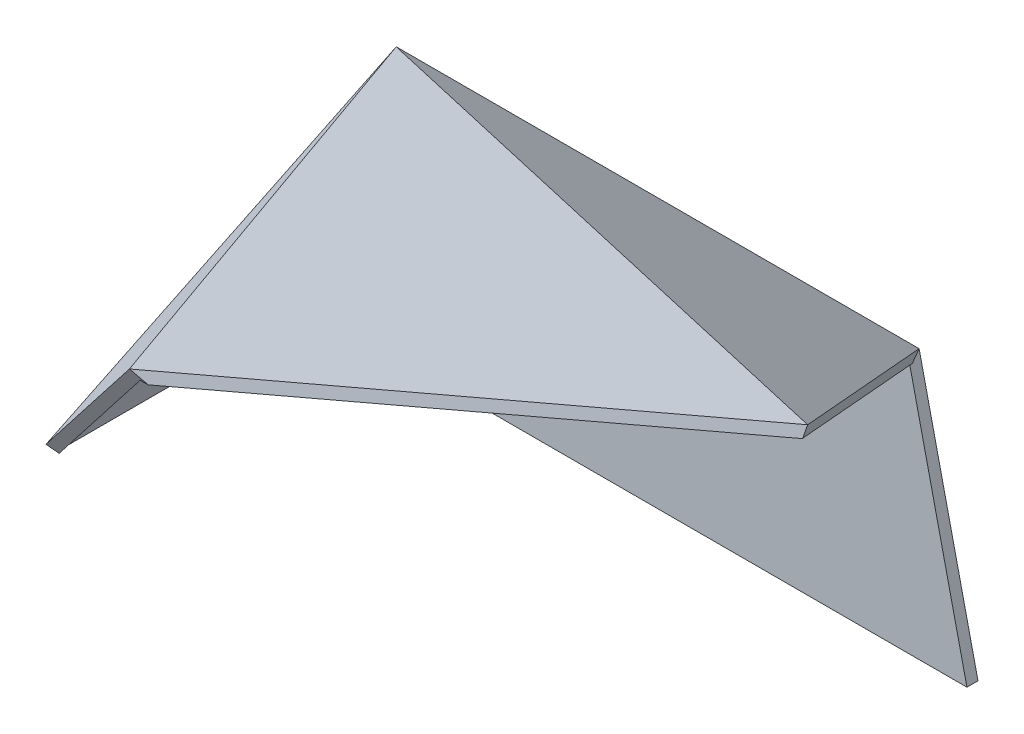
SolidWorks part; units mm, degrees
ref_plane "前视基准面" through (0, 0, 0) normal (0, 0, 1) x (1, 0, 0)
ref_plane "上视基准面" through (0, 0, 0) normal (0, 1, 0) x (1, 0, 0)
ref_plane "右视基准面" through (0, 0, 0) normal (1, 0, 0) x (0, 0, -1)
sketch "Sketch1" plane through (0, 0, 0) normal (0, 0, 1) x (1, 0, 0)
  line L0 (-295, -10) -> (-113.1586, -10)
  line L1 (-295, -10) -> (295, -10) construction
  line L2 (-113.1586, -10) -> (-129.1191, 60)
  line L3 (-129.1191, 60) -> (-270.8573, 60)
  line L4 (-270.8573, 60) -> (-295, -10)
  line L5 (-55, -10) -> (-295, -10) construction
  point P6 (-119.1255, 69.147)
  point P8 (-138.6835, -10)
  point P9 (-123.2439, 67.2585)
  point P10 (-98.3304, -10)
  point P13 (-129.1191, 68.9505)
  point P14 (-113.1586, -10)
  point P15 (-234.923, 70)
  point P16 (-260.891, 50)
  point P17 (-277.8307, 50)
  point P18 (-270.8573, 60)
  dimension "D1" = 70
extrude "Extrude1" add sketch "Sketch1" against normal blind 3
sketch "Sketch2" plane through (-260.5569, 89.8651, 0) normal (-0.9454, 0.326, 0) x (0, 0, 1)
  line L0 (0, -31.5915) -> (0, -105.6379)
  line L1 (0, -31.5915) -> (0, -105.6379) construction
  line L2 (0, -105.6379) -> (67.7928, -105.6379)
  line L5 (0, -31.5915) -> (67.7928, -105.6379)
  point P6 (0, -154.4847)
extrude "Extrude2" add sketch "Sketch2" against normal blind 3
ref_plane "Plane1" through (0, 90, 0) normal (0, -1, 0) x (-1, 0, 0)
sketch "Sketch3" plane through (0, 90, 0) normal (0, -1, 0) x (-1, 0, 0)
  line L0 (201.3797, -153.6318) -> (201.3797, -124.7992) construction
  line L2 (226.9384, -143.7928) -> (224.0406, -143.7928) construction
  point P2 (201.3797, -138.7928)
  point P4 (201.3797, -138.7928)
  dimension "D1" = 5
ref_plane "Plane4" through (0, 120, 0) normal (0, 1, 0) x (1, 0, 0)
sketch "Sketch6" plane through (0, 120, 0) normal (0, 1, 0) x (1, 0, 0)
  point P0 (-66.3616, -89.9707)
ref_plane "Plane5" through (0, 43.7249, -28.2185) normal (0, 0.8402, -0.5422) x (1, 0, 0)
sketch "Sketch7" plane through (0, 43.7249, -28.2185) normal (0, 0.8402, -0.5422) x (1, 0, 0)
  line L0 (-66.3616, -140.6648) -> (-129.1191, -30.0142)
  line L1 (-129.1191, -30.0142) -> (-270.8573, -30.0142)
  line L2 (-270.8573, -30.0142) -> (-66.3616, -140.6648)
extrude "Extrude4" add sketch "Sketch7" against normal blind 3
ref_axis "Axis1" through (-270.8573, 60, -3) along (-0.2357, -0.6833, 0.691)
ref_plane "Plane6" through (-194.9332, 134.9532, 66.9631) normal (-0.7912, 0.5478, 0.2718) x (0.225, -0.1525, 0.9623)
sketch "Sketch8" plane through (-194.9332, 134.9532, 66.9631) normal (-0.7912, 0.5478, 0.2718) x (0.225, -0.1525, 0.9623)
  line L0 (74.5289, -40.8326) -> (-72.9852, -104.6444)
  line L1 (-72.9852, -104.6444) -> (0.3827, -176.1401)
  line L2 (0.3827, -176.1401) -> (74.5289, -40.8326)
extrude "Extrude5" add sketch "Sketch8" against normal blind 3
ref_plane "Plane7" through (-30.5316, 120.3261, -10.4979) normal (-0.2451, 0.9658, -0.0843) x (0.9695, 0.2441, -0.0213)
sketch "Sketch9" plane through (-30.5316, 120.3261, -10.4979) normal (-0.2451, 0.9658, -0.0843) x (0.9695, 0.2441, -0.0213)
  line L0 (-36.9571, -100.06) -> (-176.222, -146.0899)
  line L1 (-176.222, -146.0899) -> (-247.8849, -2.2263)
  line L2 (-247.8849, -2.2263) -> (-36.9571, -100.06)
extrude "Extrude6" add sketch "Sketch9" against normal blind 3
sketch "Sketch10" plane through (-194.9332, 134.9532, 66.9631) normal (-0.7912, 0.5478, 0.2718) x (0.2235, -0.1547, 0.9624)
  line L1 (-95.6876, -88.5386) -> (16.8839, -88.5386)
  line L2 (-95.6876, -88.5386) -> (-95.6876, -178.6946)
  line L3 (-95.6876, -178.6946) -> (16.8839, -178.6946)
  line L4 (16.8839, -88.5386) -> (16.8839, -178.6946)
  point P4 (16.8839, -178.6946)
extrude "Extrude7" cut sketch "Sketch10" along normal blind 3
sketch "Sketch11" plane through (0, 0, -3) normal (0, 0, -1) x (-1, 0, 0)
  line L1 (239.3397, 70.1877) -> (313.0975, 70.1877)
  line L2 (239.3397, 70.1877) -> (239.3397, 55.4282)
  line L3 (239.3397, 55.4282) -> (313.0975, 55.4282)
  line L4 (313.0975, 70.1877) -> (313.0975, 55.4282)
extrude "Extrude8" cut sketch "Sketch11" along normal blind 3
sketch "Sketch12" plane through (0, -10, 0) normal (0, -1, 0) x (1, 0, 0)
  line L1 (-355.8844, -24.4832) -> (-188.0129, -24.4832)
  line L2 (-355.8844, -24.4832) -> (-355.8844, 171.382)
  line L3 (-355.8844, 171.382) -> (-188.0129, 171.382)
  line L4 (-188.0129, -24.4832) -> (-188.0129, 171.382)
extrude "Extrude10" cut sketch "Sketch12" along normal blind 3
sketch "Sketch13" plane through (-6.4507, -44.9577, 71.8265) normal (-0.0759, -0.529, 0.8452) x (0.9971, -0.0403, 0.0643)
  line L1 (-217.8128, 155.7733) -> (-173.2445, 155.7733)
  line L2 (-217.8128, 155.7733) -> (-217.8128, 131.2611)
  line L3 (-217.8128, 131.2611) -> (-173.2445, 131.2611)
  line L4 (-173.2445, 155.7733) -> (-173.2445, 131.2611)
extrude "Extrude11" cut sketch "Sketch13" along normal blind 3
sketch "Sketch14" plane through (25.3769, 13.2736, 78.3364) normal (0.3043, 0.1591, 0.9392) x (0.9526, -0.0508, -0.3)
  line L1 (-122.9735, 108.9795) -> (-62.7635, 108.9795)
  line L2 (-122.9735, 108.9795) -> (-122.9735, 92.9613)
  line L3 (-122.9735, 92.9613) -> (-62.7635, 92.9613)
  line L4 (-62.7635, 108.9795) -> (-62.7635, 92.9613)
extrude "Extrude12" cut sketch "Sketch14" along normal blind 3
sketch "Sketch15" plane through (-110.5731, 34.0063, 52.6931) normal (0.8698, -0.2675, -0.4145) x (-0.3962, 0.1219, -0.91)
  line L1 (-45.3554, 87.1221) -> (-30.4661, 87.1221)
  line L2 (-45.3554, 87.1221) -> (-45.3554, 100.6095)
  line L3 (-45.3554, 100.6095) -> (-30.4661, 100.6095)
  line L4 (-30.4661, 87.1221) -> (-30.4661, 100.6095)
extrude "Extrude13" cut sketch "Sketch15" along normal blind 3
